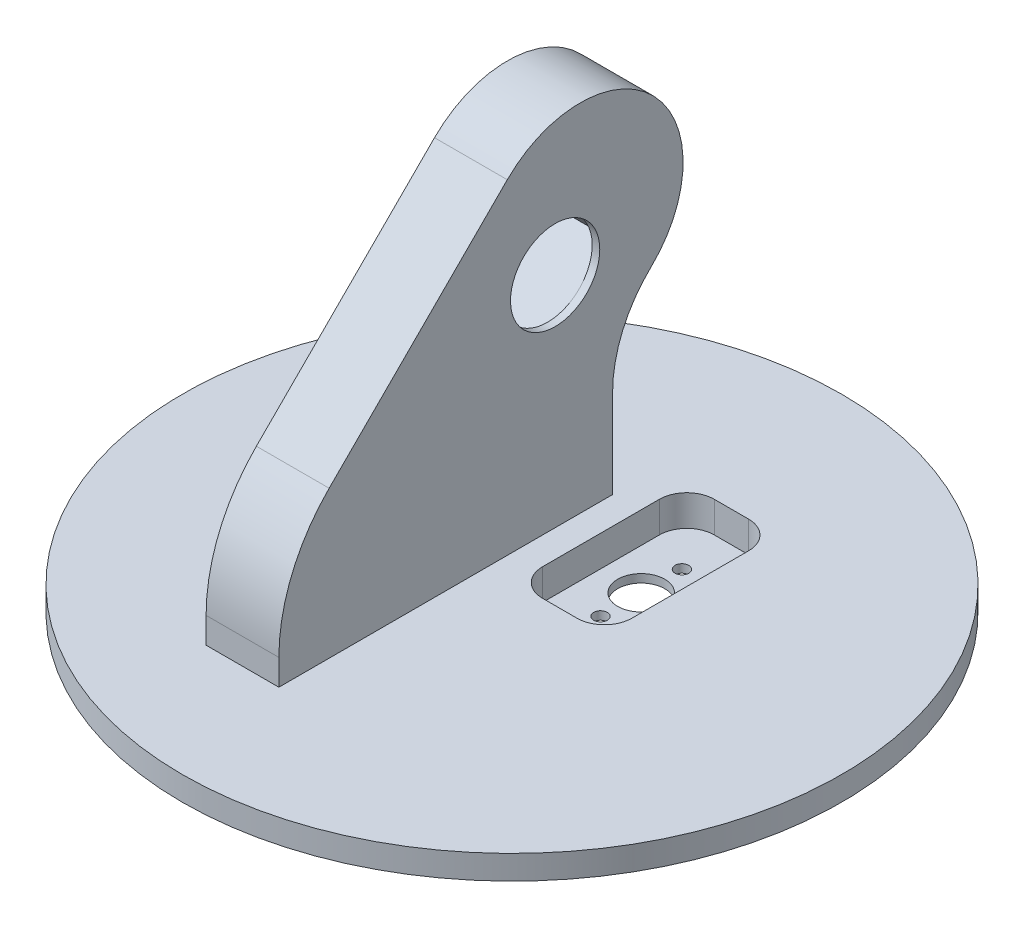
SolidWorks part; units mm, degrees
ref_plane "Front Plane" through (0, 0, 0) normal (0, 0, 1) x (1, 0, 0)
ref_plane "Top Plane" through (0, 0, 0) normal (0, 1, 0) x (1, 0, 0)
ref_plane "Right Plane" through (0, 0, 0) normal (1, 0, 0) x (0, 0, -1)
sketch "Sketch2" plane through (0, 0, 0) normal (0, 1, 0) x (1, 0, 0)
  circle A0 centre (0, 0) radius 48
  dimension "D1" = 96
extrude "Boss-Extrude1" add sketch "Sketch2" along normal blind 3.5
ref_plane "Plane1" through (-4, 0, 0) normal (1, 0, 0) x (0, 0, -1)
sketch "Sketch7" plane through (-4, 0, 0) normal (1, 0, 0) x (0, 0, -1)
  line L0 (18.6521, 16.3561) -> (18.6521, 3.5)
  line L5 (48, 3.5) -> (-48, 3.5) construction
  line L6 (-22.6311, 24.9401) -> (3.3119, 50.8831)
  line L7 (-43.5609, 3.5) -> (18.6521, 3.5)
  line L11 (-29.9535, 3.5) -> (-29.9535, 7.2624)
  arc A4 (24.252, 29.4036) -> (3.3119, 50.8831) centre (13.9185, 40.2765) ccw
  arc A5 (24.252, 29.4036) -> (18.6521, 16.3561) centre (36.6521, 16.3561) ccw
  arc A6 (-22.6311, 24.9401) -> (-29.9535, 7.2624) centre (-4.9535, 7.2624) ccw
  dimension "D1" = 25
  dimension "D4" = 30
  dimension "D3" = 18
  dimension "D5" = 45
extrude "Boss-Extrude2" add sketch "Sketch7" against normal blind 10.6 contours A5 A4 L6 L7 L0 | A4 | A4 | A4 | L6 A6 L7 region at (-4, 25.827, -1.7732)
ref_plane "Plane2" through (-6, 0, 0) normal (1, 0, 0) x (0, 0, -1)
sketch "Sketch31" plane through (-14.6, 10.4618, -5.3595) normal (-1, 0, 0) x (0, 0, 1)
  line L0 (-5.4155, 34.0546) -> (11.7496, 18.7458)
  line L1 (11.7496, 18.7458) -> (3.0968, 9.0438)
  line L2 (3.0968, 9.0438) -> (-14.0683, 24.3526)
  line L3 (-14.0683, 24.3526) -> (-5.4155, 34.0546)
  circle A0 centre (-4.9225, 24.9054) radius 6.5
  dimension "D1" = 6.5
extrude "Cut-Extrude18" cut sketch "Sketch31" against normal through all contours A0
extrude "Cut-Extrude19" cut sketch "Sketch31<3>" against normal blind 9.5 contours L0 L1 L2 L3
sketch "Sketch31<3>" plane through (-14.6, 10.4618, -5.3595) normal (-1, 0, 0) x (0, 0, 1) same geometry as "Sketch31"
sketch "Sketch32" plane through (-14.6, 0, 0) normal (-1, 0, 0) x (0, 0, 1)
  line L0 (6.3901, 29.2076) -> (-2.2627, 19.5056) construction
  circle A0 centre (-17.0806, 41.2645) radius 1
  circle A1 centre (3.9294, 22.6926) radius 1
  arc A3 (-14.6084, 40.2182) -> (-15.5944, 39.1126) centre (-10.282, 35.3672) ccw construction
  dimension "D1" = 2.5
  dimension "D2" = 2.5
extrude "Cut-Extrude20" cut sketch "Sketch32" against normal blind 4.5
sketch "Sketch33" plane through (0, 0, 0) normal (0, -1, 0) x (1, 0, 0)
  circle A0 centre (0, 0) radius 43.5
extrude "Boss-Extrude3" add sketch "Sketch33" along normal blind 2.2
sketch "Sketch34" plane through (0, 3.5, 0) normal (0, 1, 0) x (1, 0, 0)
  line L1 (0, 0.4633) -> (13, 0.4633)
  line L2 (0, 0.4633) -> (0, 25.4633)
  line L3 (0, 25.4633) -> (13, 25.4633)
  line L4 (13, 0.4633) -> (13, 25.4633)
  dimension "D1" = 25
  dimension "D2" = 13
extrude "Cut-Extrude21" cut sketch "Sketch34" against normal blind 4.5
sketch "Sketch35" plane through (70.6968, 3.5, -19.0637) normal (0, 1, 0) x (1, 0, 0)
  circle A0 centre (-64.7222, -6.2183) radius 3.43
  dimension "D1" = 6.86
extrude "Cut-Extrude22" cut sketch "Sketch35" against normal through all
fillet "Fillet1" radius 4 4 edges at (13, 1.25, -0.4633) (0, 1.25, -0.4633) (13, 1.25, -25.4633) (0, 1.25, -25.4633)
sketch "Sketch36" plane through (0, -1, 0) normal (0, 1, 0) x (1, 0, 0)
  circle A0 centre (5.9746, 18.7754) radius 1
  circle A2 centre (5.9746, 12.8454) radius 3.43 construction
  circle A3 centre (5.9746, 6.9154) radius 1
  dimension "D1" = 2.5
  dimension "D2" = 2.5
extrude "Cut-Extrude23" cut sketch "Sketch36" against normal blind 10
